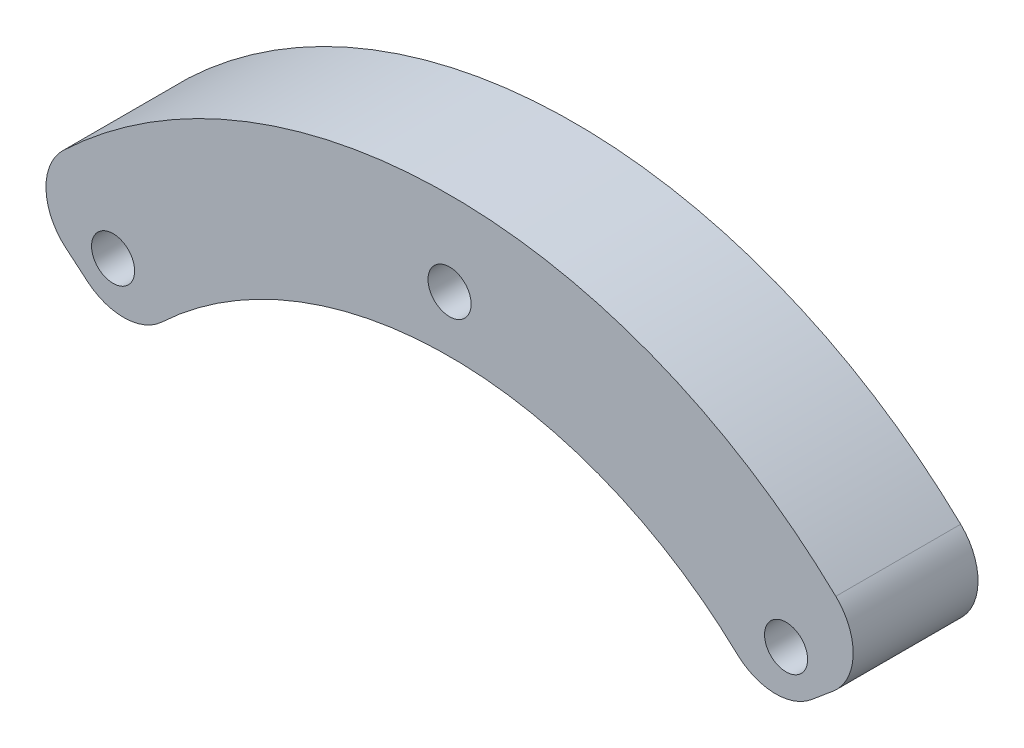
SolidWorks part; units mm, degrees
ref_plane "前视基准面" through (0, 0, 0) normal (0, 0, 1) x (1, 0, 0)
ref_plane "上视基准面" through (0, 0, 0) normal (0, 1, 0) x (1, 0, 0)
ref_plane "右视基准面" through (0, 0, 0) normal (1, 0, 0) x (0, 0, -1)
other "Configuration Table"
sketch "草图1" plane through (0, 0, 0) normal (0, 0, 1) x (1, 0, 0)
  line L0 (0, 0) -> (38.3022, 32.1394)
  line L1 (0, 0) -> (-38.3022, 32.1394)
  line L2 (0, 50) -> (0, -50) construction
  circle A0 centre (0, 0) radius 50
  circle A1 centre (0, 0) radius 37.5
  circle A2 centre (42.5, 0) radius 1.925
  circle A3 centre (30.052, -30.052) radius 1.925
  circle A4 centre (0, -42.5) radius 1.925
  circle A5 centre (-30.052, -30.052) radius 1.925
  circle A6 centre (-42.5, 0) radius 1.925
  circle A7 centre (-30.052, 30.052) radius 1.925
  circle A8 centre (0, 42.5) radius 1.925
  circle A9 centre (30.052, 30.052) radius 1.925
  point P23 (0, 0)
  dimension "D1" = 100
  dimension "D2" = 75
  dimension "D3" = 3.85
  dimension "D4" = 42.5
  dimension "D6" = 50
  dimension "D7" = 50
  dimension "D5" = 8
extrude "凸台-拉伸1" add sketch "草图1" along normal blind 11.15 contours L2 A0 L1 A1 A8 A7 | A0 L2 A8 A1 L0 A9 region at (17.9438, 38.8355, 0) region at (-17.9438, 38.8355, 0)
fillet "圆角3" radius 5 4 edges at (38.3022, 32.1394, 5.575) (28.7267, 24.1045, 5.575) (-28.7267, 24.1045, 5.575) (-38.3022, 32.1394, 5.575)
move or copy body "实体-移动/复制1" [suppressed] bodies to move or copy 106 parameters "D1"=0, "D2"=0, "D3"=0
move or copy body "实体-移动/复制2" [suppressed] bodies to move or copy 107 parameters "D1"=0, "D2"=0, "D3"=0
move or copy body "实体-移动/复制3" [suppressed] bodies to move or copy 108 parameters "D1"=0, "D2"=0, "D3"=0
move or copy body "实体-移动/复制4" [suppressed] bodies to move or copy 109 parameters "D1"=0, "D2"=0, "D3"=0
move or copy body "实体-移动/复制5" [suppressed] bodies to move or copy 110 parameters "D1"=0, "D2"=0, "D3"=0
move or copy body "实体-移动/复制6" [suppressed] bodies to move or copy 111 parameters "D1"=0, "D2"=0, "D3"=0
move or copy body "实体-移动/复制7" [suppressed] bodies to move or copy 112 parameters "D1"=0, "D2"=0, "D3"=0
move or copy body "实体-移动/复制8" [suppressed] bodies to move or copy 113 parameters "D1"=0, "D2"=0, "D3"=0
